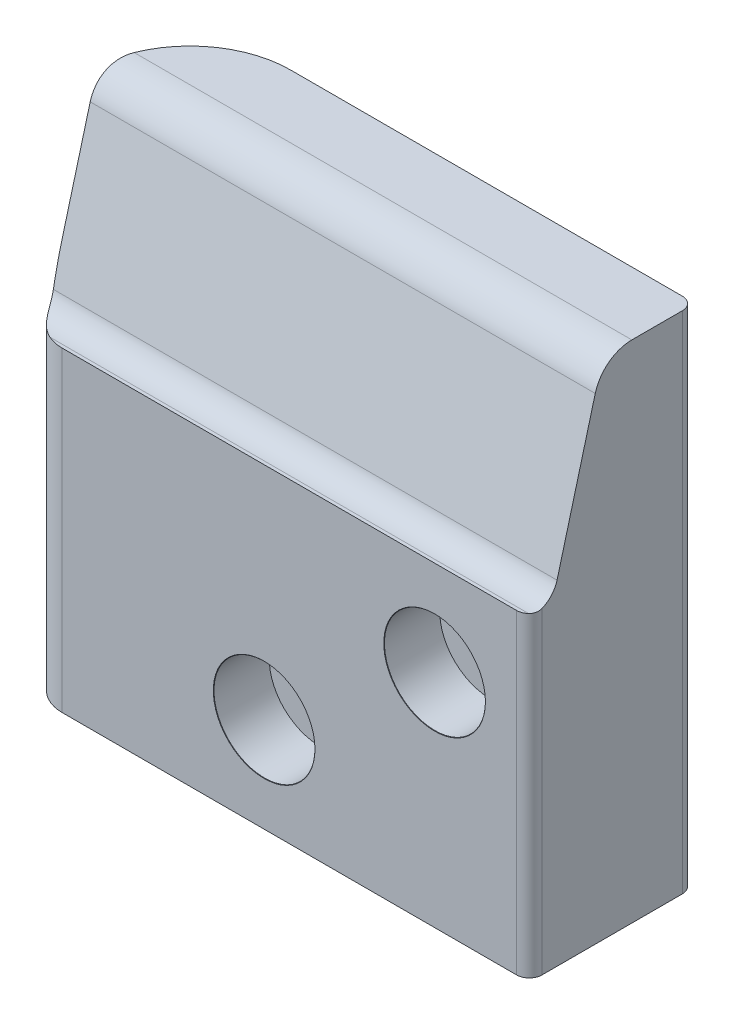
SolidWorks part; units mm, degrees
material "K110"
ref_plane "Front Plane" through (0, 0, 0) normal (0, 0, 1) x (1, 0, 0)
ref_plane "Top Plane" through (0, 0, 0) normal (0, 1, 0) x (1, 0, 0)
ref_plane "Right Plane" through (0, 0, 0) normal (1, 0, 0) x (0, 0, -1)
sketch "Sketch1" plane through (0, 0, 0) normal (1, 0, 0) x (0, 0, -1)
  line L0 (-5, 0) -> (0, 0)
  line L1 (0, 0) -> (0, -40)
  line L2 (0, -40) -> (-13.12, -40)
  line L3 (-13.12, -40) -> (-13.12, -15)
  line L4 (-13.12, -15) -> (-11.3212, -15)
  line L5 (-11.3212, -15) -> (-7.8978, -2.2235)
  arc A0 (-7.8978, -2.2235) -> (-5, 0) centre (-5, -3) cw
  dimension "D2" = 3
  dimension "D1" = 5
  dimension "D3" = 40
  dimension "D4" = 25
  dimension "D5" = 75
  dimension "D6" = 13.12
extrude "Boss-Extrude1" add sketch "Sketch1" along normal mid plane 40
fillet "Fillet1" radius 1 2 edges at (20, -20, 0) (20, -27.5, 13.12)
fillet "Fillet2" radius 2 1 edges at (0, -15, 11.3212)
fillet "Fillet3" radius 8 1 edges at (-20, -20, 0)
fillet "Fillet4" radius 3 1 edges at (-20, -27.5, 13.12)
hole_wizard "CBORE for M4 Hex Socket Head Cap Screw1" positions "Sketch8" profile "Sketch7" counterbore size "M4" standard "ISO" end condition through all
sketch "Sketch8" plane through (0, 0, 13.12) normal (0, 0, 1) x (1, 0, 0)
  line L1 (19, -15) -> (-17, -15) construction
  line L2 (19, -40) -> (19, -15) construction
  point P0 (12.5, -22.5)
  point P4 (-1, -32.5)
  point P7 (-1.5454, -32.4583)
  point P8 (12.8888, -22.5417)
  point P17 (13.9678, -15)
  dimension "D1" = 7.5
  dimension "D2" = 6.5
  dimension "D3" = 20
  dimension "D4" = 17.5
sketch "Sketch7" plane through (12.5, -22.5, 13.12) normal (1, 0, 0) x (0, -1, 0)
  line L0 (0, 0) -> (0, 13.12)
  line L1 (0, 13.12) -> (2.15, 13.12)
  line L3 (2.15, 13.12) -> (2.15, 4.4)
  line L4 (4, 4.4) -> (2.15, 4.4)
  line L5 (4, 4.4) -> (4, 0.025)
  line L6 (4, 0.025) -> (4.025, 0)
  line L7 (4.025, 0) -> (0, 0)
  line L8 (-4, 0.025) -> (-4.025, 0) construction
  line L11 (0, -6.35) -> (0, 107.95) construction
  dimension "Thru Hole Dia." = 4.3
  dimension "Thru Hole Depth" = 13.12
  dimension "C'Bore Dia." = 8
  dimension "C'Bore Depth" = 4.4
  dimension "Near C'Sink Dia." = 8.05
  dimension "Near C'Sink Angle" = 90
